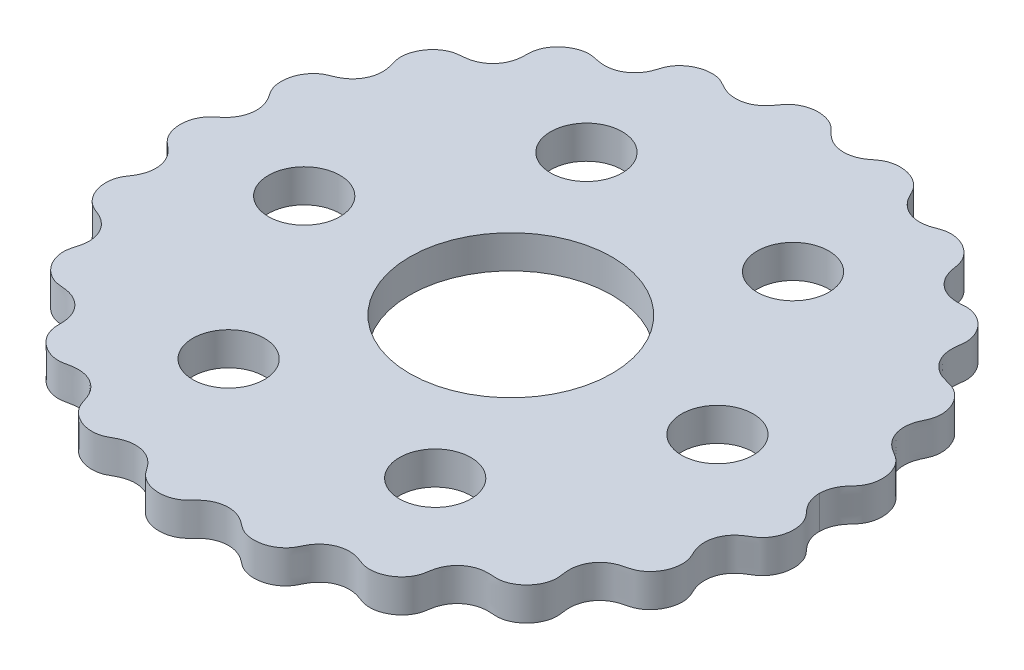
SolidWorks part; units mm, degrees
ref_plane "Front Plane" through (0, 0, 0) normal (0, 0, 1) x (1, 0, 0)
ref_plane "Top Plane" through (0, 0, 0) normal (0, 1, 0) x (1, 0, 0)
ref_plane "Right Plane" through (0, 0, 0) normal (1, 0, 0) x (0, 0, -1)
sketch "Sketch1" plane through (0, 0, 0) normal (0, 1, 0) x (1, 0, 0)
  line L0 (-58.2641, -0.8721) -> (57.7359, -0.8721) construction
  line L1 (1.7359, -0.8721) -> (1.7359, 57.2699) construction
  line L2 (1.7359, -0.8721) -> (1.7359, -59.0142) construction
  line L3 (-0.2641, -69.7644) -> (-0.2641, 70.5566) construction
  circle A0 centre (-0.2641, -0.8721) radius 63 construction
  circle A23 centre (1.7359, -0.8721) radius 37.5 construction
  circle A24 centre (-35.7641, -0.8721) radius 6.5
  circle A25 centre (-17.0141, 31.6038) radius 6.5
  circle A26 centre (20.4859, 31.6038) radius 6.5
  circle A27 centre (39.2359, -0.8721) radius 6.5
  circle A28 centre (20.4859, -33.3481) radius 6.5
  circle A29 centre (-17.0141, -33.3481) radius 6.5
  circle A37 centre (1.7359, -0.8721) radius 18.35
  spline S0 degree 4 poles (57.7091, 12.498) (57.878, 12.389) (58.2202, 12.1788) (58.75, 11.8893) (59.3907, 11.3973) (60.0214, 10.7095) (60.5813, 9.8085) (61.0058, 8.6748) (61.1955, 7.3302) (61.0908, 6.0677) (60.7435, 4.9487) (60.2801, 4.1321) (59.83, 3.5913) (59.4315, 3.1644) (59.1244, 2.811) (58.7965, 2.3918) (58.5194, 1.9674) (58.2923, 1.5442) (58.1126, 1.1275) (57.9906, 0.7856) (57.8914, 0.4364) (57.8251, 0.1259) (57.7831, -0.1439) (57.7603, -0.3468) (57.7488, -0.4924) (57.7402, -0.6503) (57.7355, -0.8102) (57.7353, -0.9181) (57.7394, -1.0706) (57.7465, -1.2185) (57.7568, -1.3606) (57.7782, -1.564) (57.8193, -1.8402) (57.8855, -2.1574) (57.9855, -2.5144) (58.1092, -2.8638) (58.2558, -3.2043) (58.4393, -3.5643) (58.665, -3.9391) (58.9372, -4.3234) (59.2571, -4.7132) (59.5962, -5.0858) (59.9358, -5.4582) (60.3214, -5.9576) (60.6604, -6.5603) (60.9245, -7.2626) (61.13, -8.2337) (61.1724, -9.3303) (60.9716, -10.5841) (60.4579, -11.8202) (59.7514, -12.811) (58.9127, -13.5486) (58.0252, -14.0251) (57.0958, -14.6302) (56.2107, -15.47) (55.4688, -16.595) (55.0111, -17.9962) (54.951, -19.3674) (55.1999, -20.6093) (55.6274, -21.6646) (56.103, -22.5667) (56.3981, -23.6738) (56.4238, -24.9379) (56.1285, -26.2986) (55.456, -27.6601) (54.5568, -28.7133) (53.5462, -29.4477) (52.5224, -29.8657) (51.5811, -30.0467) (50.5652, -30.3482) (49.5187, -30.8634) (48.5105, -31.6766) (47.6661, -32.8195) (47.2272, -33.9443) (47.0641, -34.9162) (47.0436, -35.6628) (47.0698, -36.1739) (47.1288, -36.6821) (47.2056, -37.1875) (47.2615, -37.6964) (47.2635, -38.2089) (47.2028, -38.7861) (47.0569, -39.4186) (46.8065, -40.0912) (46.4345, -40.7833) (45.8852, -41.5463) (45.1085, -42.3223) (44.1594, -42.9564) (43.1695, -43.3403) (42.3593, -43.4895) (41.7709, -43.5172) (41.3006, -43.4968) (40.8315, -43.4622) (40.3613, -43.4427) (39.825, -43.4512) (39.2256, -43.5117) (38.3919, -43.6889) (37.3515, -44.1083) (36.2639, -44.8727) (35.3819, -45.9667) (34.897, -47.0193) (34.6633, -47.8867) (34.5491, -48.5206) (34.4731, -49.0298) (34.371, -49.5352) (34.2144, -50.027) (33.9034, -50.729) (33.3353, -51.5818) (32.4167, -52.4771) (31.0868, -53.2449) (29.8522, -53.5928) (28.8295, -53.6584) (28.0661, -53.5767) (27.5619, -53.4665) (27.0731, -53.3022) (26.5941, -53.1133) (26.1093, -52.9391) (25.6142, -52.7956) (24.8615, -52.6402) (23.8372, -52.5777) (22.5776, -52.7745) (21.2036, -53.4123) (20.2572, -54.2235) (19.66, -54.9905) (19.2905, -55.6079) (19.0722, -56.0249) (18.8677, -56.4484) (18.6502, -56.8659) (18.3955, -57.2625) (18.1023, -57.6313) (17.6128, -58.1373) (16.8639, -58.7066) (15.9465, -59.159) (14.8862, -59.4436) (13.9507, -59.5378) (13.1654, -59.5139) (12.4577, -59.3944) (11.837, -59.2046) (11.3067, -58.9685) (10.8639, -58.7106) (10.4512, -58.4077) (10.0519, -58.0885) (9.6412, -57.7832) (9.2117, -57.505) (8.5549, -57.1495) (7.6317, -56.8048) (6.4381, -56.6225) (5.0261, -56.7823) (3.8178, -57.2488) (2.8483, -57.8975) (2.0793, -58.6266) (1.4519, -59.3513) (0.578, -60.0289) (-0.5633, -60.537) (-1.925, -60.7891) (-3.4404, -60.6907) (-4.7664, -60.2661) (-5.8482, -59.6118) (-6.6595, -58.8026) (-7.203, -57.9397) (-7.9031, -57.0419) (-8.8542, -56.2054) (-10.0718, -55.5718) (-11.5141, -55.2676) (-12.8593, -55.3476) (-14.0291, -55.6943) (-15.0179, -56.1965) (-15.8742, -56.7269) (-16.9324, -57.0844) (-18.1437, -57.2009) (-19.4713, -57.0276) (-20.831, -56.5084) (-21.9495, -55.7397) (-22.7899, -54.8119) (-23.3378, -53.8167) (-23.6076, -52.8425) (-23.9936, -51.783) (-24.6344, -50.7033) (-25.5969, -49.7156) (-26.8973, -48.9648) (-28.2339, -48.6251) (-29.4894, -48.61) (-30.6, -48.8054) (-31.5785, -49.0589) (-32.7144, -49.082) (-33.938, -48.8181) (-35.1631, -48.2338) (-36.2926, -47.3159) (-37.1064, -46.2527) (-37.6111, -45.1455) (-37.8307, -44.0504) (-37.7995, -43.0436) (-37.8589, -41.9361) (-38.1436, -40.7497) (-38.7469, -39.5447) (-39.7315, -38.4478) (-40.889, -37.7101) (-42.0889, -37.3047) (-43.2166, -37.1473) (-44.2356, -37.1081) (-45.342, -36.81) (-46.4495, -36.2003) (-47.4805, -35.2642) (-48.3229, -34.0011) (-48.786, -32.6958) (-48.9158, -31.4533) (-48.7836, -30.4772) (-48.5691, -29.7915) (-48.37, -29.1026) (-48.1967, -28.3012) (-48.1293, -27.2576) (-48.3283, -25.9778) (-48.8967, -24.6752) (-49.6508, -23.7326) (-50.4112, -23.1055) (-51.0474, -22.7144) (-51.5032, -22.4815) (-51.9728, -22.2785) (-52.449, -22.0923) (-52.9176, -21.8863) (-53.3624, -21.6318) (-53.832, -21.2906) (-54.3068, -20.8479) (-54.7641, -20.2948) (-55.1775, -19.6266) (-55.5635, -18.7694) (-55.8473, -17.7088) (-55.9219, -16.5698) (-55.7594, -15.5205) (-55.4834, -14.7443) (-55.2132, -14.2209) (-54.9604, -13.8237) (-54.6959, -13.4349) (-54.4439, -13.0374) (-54.1832, -12.5687) (-53.9359, -12.0193) (-53.6724, -11.2087) (-53.5424, -10.2882) (-53.5821, -9.3512) (-53.794, -8.4338) (-54.0692, -7.7195) (-54.4733, -6.9919) (-54.9442, -6.3815) (-55.4436, -5.8807) (-55.9354, -5.465) (-56.3384, -5.1445) (-56.7251, -4.8034) (-57.0727, -4.4218) (-57.3568, -4.0324) (-57.5855, -3.6469) (-57.7674, -3.2749) (-57.9102, -2.9223) (-58.029, -2.5612) (-58.1239, -2.1926) (-58.1861, -1.8664) (-58.2246, -1.5821) (-58.2446, -1.3733) (-58.2542, -1.228) (-58.2609, -1.076) (-58.2645, -0.9274) (-58.2646, -0.8251) (-58.2612, -0.682) (-58.2553, -0.539) (-58.2469, -0.4008) (-58.2292, -0.2042) (-58.1952, 0.0622) (-58.1403, 0.3703) (-58.0565, 0.7175) (-57.9516, 1.0593) (-57.8255, 1.3936) (-57.6656, 1.747) (-57.4652, 2.1143) (-57.2171, 2.4887) (-56.9137, 2.8602) (-56.5739, 3.1987) (-56.2061, 3.5056) (-55.8327, 3.8052) (-55.4709, 4.1192) (-55.0869, 4.4965) (-54.6983, 4.9508) (-54.2262, 5.6417) (-53.7783, 6.6204) (-53.5163, 7.8522) (-53.5816, 9.0569) (-53.8273, 9.992) (-54.1104, 10.6706) (-54.343, 11.1216) (-54.6063, 11.5553) (-54.8896, 11.9756) (-55.1688, 12.399) (-55.4088, 12.8467) (-55.5509, 13.2002) (-55.629, 13.4414) (-55.6639, 13.5633) knots 0 0 0 0 0 0.003358 0.006716 0.010075 0.013433 0.018886 0.024339 0.030148 0.035957 0.039866 0.043775 0.045729 0.047683 0.049638 0.051592 0.054624 0.05614 0.057656 0.059172 0.060688 0.062203 0.062961 0.063719 0.064151 0.064583 0.065447 0.066221 0.066608 0.066995 0.067769 0.068543 0.070091 0.071639 0.073187 0.074735 0.076283 0.077831 0.079936 0.082042 0.084147 0.086253 0.088359 0.090464 0.094675 0.097759 0.100843 0.10701 0.112905 0.118801 0.122998 0.127195 0.131392 0.135589 0.141508 0.147428 0.153675 0.159922 0.164171 0.16842 0.172669 0.176918 0.18314 0.189363 0.195705 0.202048 0.206045 0.210043 0.21404 0.218037 0.223723 0.229409 0.235467 0.241525 0.243662 0.245799 0.247936 0.250073 0.25221 0.254347 0.256484 0.258621 0.261894 0.265168 0.268441 0.271715 0.277567 0.283419 0.287351 0.289317 0.291283 0.293249 0.295215 0.297181 0.299147 0.302208 0.305269 0.311391 0.317768 0.324145 0.328449 0.330601 0.332753 0.334905 0.337058 0.33921 0.341362 0.347715 0.354068 0.360421 0.366774 0.368926 0.371078 0.37323 0.375382 0.377534 0.379686 0.381838 0.383991 0.390367 0.396744 0.402867 0.408989 0.410955 0.412921 0.414887 0.416852 0.418818 0.420784 0.42275 0.424716 0.430568 0.43642 0.439694 0.442968 0.446241 0.449515 0.451652 0.453789 0.455926 0.458063 0.4602 0.462337 0.464473 0.46661 0.472669 0.478727 0.484412 0.490098 0.494096 0.498093 0.50209 0.506088 0.51243 0.518773 0.524995 0.531217 0.535466 0.539716 0.543965 0.548214 0.554461 0.560708 0.566627 0.572547 0.576744 0.580941 0.585138 0.589335 0.59523 0.601125 0.607293 0.61346 0.617671 0.621882 0.626094 0.630305 0.636497 0.642688 0.64888 0.655072 0.659283 0.663494 0.667705 0.671916 0.678084 0.684251 0.690147 0.696042 0.700239 0.704436 0.708633 0.71283 0.718749 0.724669 0.730916 0.737163 0.741412 0.745661 0.74991 0.754159 0.760382 0.766604 0.772946 0.779289 0.783286 0.787284 0.789282 0.791281 0.795279 0.800964 0.80665 0.812708 0.818766 0.820903 0.82304 0.825177 0.827314 0.829451 0.831588 0.833725 0.835862 0.839135 0.842409 0.845683 0.848956 0.854808 0.860661 0.864592 0.866558 0.868524 0.87049 0.872456 0.874422 0.876388 0.879449 0.88251 0.888632 0.891821 0.895009 0.898198 0.901386 0.90569 0.907842 0.909994 0.912147 0.914299 0.916451 0.918603 0.920191 0.921779 0.923368 0.924956 0.926544 0.928132 0.928926 0.929721 0.930118 0.930515 0.931309 0.932055 0.932428 0.932802 0.933548 0.934294 0.935787 0.937279 0.938772 0.940265 0.941757 0.94325 0.945251 0.947252 0.949253 0.951254 0.953255 0.955255 0.957256 0.959257 0.962245 0.965233 0.971209 0.97713 0.983052 0.98517 0.987289 0.989407 0.991526 0.993644 0.995763 0.997881 1 1 1 1 1 construction
  spline S1 degree 4 poles (57.7359, -0.8721) (57.7359, -0.9122) (57.7367, -0.9728) (57.7394, -1.0706) (57.7465, -1.2185) (57.7568, -1.3606) (57.7782, -1.564) (57.8193, -1.8402) (57.8855, -2.1574) (57.9855, -2.5144) (58.1092, -2.8638) (58.2558, -3.2043) (58.4393, -3.5643) (58.665, -3.9391) (58.9372, -4.3234) (59.2571, -4.7132) (59.5962, -5.0858) (59.9358, -5.4582) (60.3214, -5.9576) (60.6604, -6.5603) (60.9245, -7.2626) (61.13, -8.2337) (61.1724, -9.3303) (60.9716, -10.5841) (60.4579, -11.8202) (59.7514, -12.811) (58.9127, -13.5486) (58.0252, -14.0251) (57.0958, -14.6302) (56.2107, -15.47) (55.4688, -16.595) (55.0111, -17.9962) (54.951, -19.3674) (55.1999, -20.6093) (55.6274, -21.6646) (56.103, -22.5667) (56.3981, -23.6738) (56.4238, -24.9379) (56.1285, -26.2986) (55.456, -27.6601) (54.5568, -28.7133) (53.5462, -29.4477) (52.5224, -29.8657) (51.5811, -30.0467) (50.5652, -30.3482) (49.5187, -30.8634) (48.5105, -31.6766) (47.6661, -32.8195) (47.2272, -33.9443) (47.0641, -34.9162) (47.0436, -35.6628) (47.0698, -36.1739) (47.1288, -36.6821) (47.2056, -37.1875) (47.2615, -37.6964) (47.2635, -38.2089) (47.2028, -38.7861) (47.0569, -39.4186) (46.8065, -40.0912) (46.4345, -40.7833) (45.8852, -41.5463) (45.1085, -42.3223) (44.1594, -42.9564) (43.1695, -43.3403) (42.3593, -43.4895) (41.7709, -43.5172) (41.3006, -43.4968) (40.8315, -43.4622) (40.3613, -43.4427) (39.825, -43.4512) (39.2256, -43.5117) (38.3919, -43.6889) (37.3515, -44.1083) (36.2639, -44.8727) (35.3819, -45.9667) (34.897, -47.0193) (34.6633, -47.8867) (34.5491, -48.5206) (34.4731, -49.0298) (34.371, -49.5352) (34.2144, -50.027) (33.9034, -50.729) (33.3353, -51.5818) (32.4167, -52.4771) (31.0868, -53.2449) (29.8522, -53.5928) (28.8295, -53.6584) (28.0661, -53.5767) (27.5619, -53.4665) (27.0731, -53.3022) (26.5941, -53.1133) (26.1093, -52.9391) (25.6142, -52.7956) (24.8615, -52.6402) (23.8372, -52.5777) (22.5776, -52.7745) (21.2036, -53.4123) (20.2572, -54.2235) (19.66, -54.9905) (19.2905, -55.6079) (19.0722, -56.0249) (18.8677, -56.4484) (18.6502, -56.8659) (18.3955, -57.2625) (18.1023, -57.6313) (17.6128, -58.1373) (16.8639, -58.7066) (15.9465, -59.159) (14.8862, -59.4436) (13.9507, -59.5378) (13.1654, -59.5139) (12.4577, -59.3944) (11.837, -59.2046) (11.3067, -58.9685) (10.8639, -58.7106) (10.4512, -58.4077) (10.0519, -58.0885) (9.6412, -57.7832) (9.2117, -57.505) (8.5549, -57.1495) (7.6317, -56.8048) (6.4381, -56.6225) (5.0261, -56.7823) (3.8178, -57.2488) (2.8483, -57.8975) (2.0793, -58.6266) (1.4519, -59.3513) (0.578, -60.0289) (-0.5633, -60.537) (-1.925, -60.7891) (-3.4404, -60.6907) (-4.7664, -60.2661) (-5.8482, -59.6118) (-6.6595, -58.8026) (-7.203, -57.9397) (-7.9031, -57.0419) (-8.8542, -56.2054) (-10.0718, -55.5718) (-11.5141, -55.2676) (-12.8593, -55.3476) (-14.0291, -55.6943) (-15.0179, -56.1965) (-15.8742, -56.7269) (-16.9324, -57.0844) (-18.1437, -57.2009) (-19.4713, -57.0276) (-20.831, -56.5084) (-21.9495, -55.7397) (-22.7899, -54.8119) (-23.3378, -53.8167) (-23.6076, -52.8425) (-23.9936, -51.783) (-24.6344, -50.7033) (-25.5969, -49.7156) (-26.8973, -48.9648) (-28.2339, -48.6251) (-29.4894, -48.61) (-30.6, -48.8054) (-31.5785, -49.0589) (-32.7144, -49.082) (-33.938, -48.8181) (-35.1631, -48.2338) (-36.2926, -47.3159) (-37.1064, -46.2527) (-37.6111, -45.1455) (-37.8307, -44.0504) (-37.7995, -43.0436) (-37.8589, -41.9361) (-38.1436, -40.7497) (-38.7469, -39.5447) (-39.7315, -38.4478) (-40.889, -37.7101) (-42.0889, -37.3047) (-43.2166, -37.1473) (-44.2356, -37.1081) (-45.342, -36.81) (-46.4495, -36.2003) (-47.4805, -35.2642) (-48.3229, -34.0011) (-48.786, -32.6958) (-48.9158, -31.4533) (-48.7836, -30.4772) (-48.5691, -29.7915) (-48.37, -29.1026) (-48.1967, -28.3012) (-48.1293, -27.2576) (-48.3283, -25.9778) (-48.8967, -24.6752) (-49.6508, -23.7326) (-50.4112, -23.1055) (-51.0474, -22.7144) (-51.5032, -22.4815) (-51.9728, -22.2785) (-52.449, -22.0923) (-52.9176, -21.8863) (-53.3624, -21.6318) (-53.832, -21.2906) (-54.3068, -20.8479) (-54.7641, -20.2948) (-55.1775, -19.6266) (-55.5635, -18.7694) (-55.8473, -17.7088) (-55.9219, -16.5698) (-55.7594, -15.5205) (-55.4834, -14.7443) (-55.2132, -14.2209) (-54.9604, -13.8237) (-54.6959, -13.4349) (-54.4439, -13.0374) (-54.1832, -12.5687) (-53.9359, -12.0193) (-53.6724, -11.2087) (-53.5424, -10.2882) (-53.5821, -9.3512) (-53.794, -8.4338) (-54.0692, -7.7195) (-54.4733, -6.9919) (-54.9442, -6.3815) (-55.4436, -5.8807) (-55.9354, -5.465) (-56.3384, -5.1445) (-56.7251, -4.8034) (-57.0727, -4.4218) (-57.3568, -4.0324) (-57.5855, -3.6469) (-57.7674, -3.2749) (-57.9102, -2.9223) (-58.029, -2.5612) (-58.1239, -2.1926) (-58.1861, -1.8664) (-58.2246, -1.5821) (-58.2446, -1.3733) (-58.2542, -1.228) (-58.2609, -1.076) (-58.2633, -0.9749) (-58.2641, -0.9133) (-58.2641, -0.8721) knots 0.065447 0.065447 0.065447 0.065447 0.065447 0.066221 0.066608 0.066995 0.067769 0.068543 0.070091 0.071639 0.073187 0.074735 0.076283 0.077831 0.079936 0.082042 0.084147 0.086253 0.088359 0.090464 0.094675 0.097759 0.100843 0.10701 0.112905 0.118801 0.122998 0.127195 0.131392 0.135589 0.141508 0.147428 0.153675 0.159922 0.164171 0.16842 0.172669 0.176918 0.18314 0.189363 0.195705 0.202048 0.206045 0.210043 0.21404 0.218037 0.223723 0.229409 0.235467 0.241525 0.243662 0.245799 0.247936 0.250073 0.25221 0.254347 0.256484 0.258621 0.261894 0.265168 0.268441 0.271715 0.277567 0.283419 0.287351 0.289317 0.291283 0.293249 0.295215 0.297181 0.299147 0.302208 0.305269 0.311391 0.317768 0.324145 0.328449 0.330601 0.332753 0.334905 0.337058 0.33921 0.341362 0.347715 0.354068 0.360421 0.366774 0.368926 0.371078 0.37323 0.375382 0.377534 0.379686 0.381838 0.383991 0.390367 0.396744 0.402867 0.408989 0.410955 0.412921 0.414887 0.416852 0.418818 0.420784 0.42275 0.424716 0.430568 0.43642 0.439694 0.442968 0.446241 0.449515 0.451652 0.453789 0.455926 0.458063 0.4602 0.462337 0.464473 0.46661 0.472669 0.478727 0.484412 0.490098 0.494096 0.498093 0.50209 0.506088 0.51243 0.518773 0.524995 0.531217 0.535466 0.539716 0.543965 0.548214 0.554461 0.560708 0.566627 0.572547 0.576744 0.580941 0.585138 0.589335 0.59523 0.601125 0.607293 0.61346 0.617671 0.621882 0.626094 0.630305 0.636497 0.642688 0.64888 0.655072 0.659283 0.663494 0.667705 0.671916 0.678084 0.684251 0.690147 0.696042 0.700239 0.704436 0.708633 0.71283 0.718749 0.724669 0.730916 0.737163 0.741412 0.745661 0.74991 0.754159 0.760382 0.766604 0.772946 0.779289 0.783286 0.787284 0.789282 0.791281 0.795279 0.800964 0.80665 0.812708 0.818766 0.820903 0.82304 0.825177 0.827314 0.829451 0.831588 0.833725 0.835862 0.839135 0.842409 0.845683 0.848956 0.854808 0.860661 0.864592 0.866558 0.868524 0.87049 0.872456 0.874422 0.876388 0.879449 0.88251 0.888632 0.891821 0.895009 0.898198 0.901386 0.90569 0.907842 0.909994 0.912147 0.914299 0.916451 0.918603 0.920191 0.921779 0.923368 0.924956 0.926544 0.928132 0.928926 0.929721 0.930118 0.930515 0.931309 0.931309 0.931309 0.931309 0.931309
  spline S2 degree 4 poles (57.7359, -0.8721) (57.7359, -0.832) (57.7367, -0.7715) (57.7394, -0.6736) (57.7465, -0.5257) (57.7568, -0.3837) (57.7782, -0.1803) (57.8193, 0.0959) (57.8855, 0.4131) (57.9855, 0.7702) (58.1092, 1.1196) (58.2558, 1.4601) (58.4393, 1.82) (58.665, 2.1948) (58.9372, 2.5792) (59.2571, 2.9689) (59.5962, 3.3416) (59.9358, 3.7139) (60.3214, 4.2134) (60.6604, 4.8161) (60.9245, 5.5184) (61.13, 6.4894) (61.1724, 7.586) (60.9716, 8.8398) (60.4579, 10.0759) (59.7514, 11.0668) (58.9127, 11.8044) (58.0252, 12.2808) (57.0958, 12.886) (56.2107, 13.7258) (55.4688, 14.8507) (55.0111, 16.2519) (54.951, 17.6231) (55.1999, 18.865) (55.6274, 19.9203) (56.103, 20.8224) (56.3981, 21.9296) (56.4238, 23.1937) (56.1285, 24.5544) (55.456, 25.9158) (54.5568, 26.9691) (53.5462, 27.7034) (52.5224, 28.1215) (51.5811, 28.3025) (50.5652, 28.6039) (49.5187, 29.1192) (48.5105, 29.9323) (47.6661, 31.0752) (47.2272, 32.2) (47.0641, 33.1719) (47.0436, 33.9185) (47.0698, 34.4296) (47.1288, 34.9379) (47.2056, 35.4433) (47.2615, 35.9521) (47.2635, 36.4646) (47.2028, 37.0419) (47.0569, 37.6744) (46.8065, 38.347) (46.4345, 39.0391) (45.8852, 39.8021) (45.1085, 40.578) (44.1594, 41.2122) (43.1695, 41.5961) (42.3593, 41.7452) (41.7709, 41.7729) (41.3006, 41.7526) (40.8315, 41.7179) (40.3613, 41.6984) (39.825, 41.707) (39.2256, 41.7675) (38.3919, 41.9446) (37.3515, 42.3641) (36.2639, 43.1285) (35.3819, 44.2224) (34.897, 45.2751) (34.6633, 46.1425) (34.5491, 46.7763) (34.4731, 47.2855) (34.371, 47.791) (34.2144, 48.2827) (33.9034, 48.9848) (33.3353, 49.8376) (32.4167, 50.7328) (31.0868, 51.5006) (29.8522, 51.8486) (28.8295, 51.9142) (28.0661, 51.8325) (27.5619, 51.7222) (27.0731, 51.558) (26.5941, 51.369) (26.1093, 51.1948) (25.6142, 51.0513) (24.8615, 50.896) (23.8372, 50.8335) (22.5776, 51.0303) (21.2036, 51.6681) (20.2572, 52.4793) (19.66, 53.2463) (19.2905, 53.8637) (19.0722, 54.2807) (18.8677, 54.7042) (18.6502, 55.1217) (18.3955, 55.5182) (18.1023, 55.8871) (17.6128, 56.3931) (16.8639, 56.9623) (15.9465, 57.4147) (14.8862, 57.6993) (13.9507, 57.7936) (13.1654, 57.7697) (12.4577, 57.6502) (11.837, 57.4604) (11.3067, 57.2243) (10.8639, 56.9663) (10.4512, 56.6635) (10.0519, 56.3442) (9.6412, 56.039) (9.2117, 55.7608) (8.5549, 55.4052) (7.6317, 55.0605) (6.4381, 54.8783) (5.0261, 55.038) (3.8178, 55.5046) (2.8483, 56.1532) (2.0793, 56.8824) (1.4519, 57.607) (0.578, 58.2846) (-0.5633, 58.7927) (-1.925, 59.0448) (-3.4404, 58.9465) (-4.7664, 58.5219) (-5.8482, 57.8675) (-6.6595, 57.0584) (-7.203, 56.1955) (-7.9031, 55.2976) (-8.8542, 54.4611) (-10.0718, 53.8275) (-11.5141, 53.5233) (-12.8593, 53.6033) (-14.0291, 53.95) (-15.0179, 54.4523) (-15.8742, 54.9827) (-16.9324, 55.3402) (-18.1437, 55.4566) (-19.4713, 55.2834) (-20.831, 54.7642) (-21.9495, 53.9955) (-22.7899, 53.0677) (-23.3378, 52.0724) (-23.6076, 51.0983) (-23.9936, 50.0387) (-24.6344, 48.959) (-25.5969, 47.9713) (-26.8973, 47.2206) (-28.2339, 46.8809) (-29.4894, 46.8658) (-30.6, 47.0612) (-31.5785, 47.3147) (-32.7144, 47.3378) (-33.938, 47.0739) (-35.1631, 46.4896) (-36.2926, 45.5716) (-37.1064, 44.5085) (-37.6111, 43.4013) (-37.8307, 42.3061) (-37.7995, 41.2994) (-37.8589, 40.1919) (-38.1436, 39.0054) (-38.7469, 37.8004) (-39.7315, 36.7035) (-40.889, 35.9659) (-42.0889, 35.5604) (-43.2166, 35.4031) (-44.2356, 35.3638) (-45.342, 35.0658) (-46.4495, 34.4561) (-47.4805, 33.52) (-48.3229, 32.2568) (-48.786, 30.9516) (-48.9158, 29.709) (-48.7836, 28.733) (-48.5691, 28.0472) (-48.37, 27.3583) (-48.1967, 26.557) (-48.1293, 25.5134) (-48.3283, 24.2335) (-48.8967, 22.9309) (-49.6508, 21.9883) (-50.4112, 21.3612) (-51.0474, 20.9701) (-51.5032, 20.7373) (-51.9728, 20.5342) (-52.449, 20.3481) (-52.9176, 20.1421) (-53.3624, 19.8875) (-53.832, 19.5464) (-54.3068, 19.1037) (-54.7641, 18.5505) (-55.1775, 17.8824) (-55.5635, 17.0251) (-55.8473, 15.9646) (-55.9219, 14.8255) (-55.7594, 13.7763) (-55.4834, 13) (-55.2132, 12.4766) (-54.9604, 12.0795) (-54.6959, 11.6906) (-54.4439, 11.2931) (-54.1832, 10.8244) (-53.9359, 10.2751) (-53.6724, 9.4644) (-53.5424, 8.544) (-53.5821, 7.607) (-53.794, 6.6896) (-54.0692, 5.9752) (-54.4733, 5.2476) (-54.9442, 4.6372) (-55.4436, 4.1365) (-55.9354, 3.7207) (-56.3384, 3.4003) (-56.7251, 3.0592) (-57.0727, 2.6775) (-57.3568, 2.2881) (-57.5855, 1.9027) (-57.7674, 1.5307) (-57.9102, 1.1781) (-58.029, 0.8169) (-58.1239, 0.4484) (-58.1861, 0.1221) (-58.2246, -0.1622) (-58.2446, -0.3709) (-58.2542, -0.5163) (-58.2609, -0.6682) (-58.2633, -0.7694) (-58.2641, -0.831) (-58.2641, -0.8721) knots 0.065447 0.065447 0.065447 0.065447 0.065447 0.066221 0.066608 0.066995 0.067769 0.068543 0.070091 0.071639 0.073187 0.074735 0.076283 0.077831 0.079936 0.082042 0.084147 0.086253 0.088359 0.090464 0.094675 0.097759 0.100843 0.10701 0.112905 0.118801 0.122998 0.127195 0.131392 0.135589 0.141508 0.147428 0.153675 0.159922 0.164171 0.16842 0.172669 0.176918 0.18314 0.189363 0.195705 0.202048 0.206045 0.210043 0.21404 0.218037 0.223723 0.229409 0.235467 0.241525 0.243662 0.245799 0.247936 0.250073 0.25221 0.254347 0.256484 0.258621 0.261894 0.265168 0.268441 0.271715 0.277567 0.283419 0.287351 0.289317 0.291283 0.293249 0.295215 0.297181 0.299147 0.302208 0.305269 0.311391 0.317768 0.324145 0.328449 0.330601 0.332753 0.334905 0.337058 0.33921 0.341362 0.347715 0.354068 0.360421 0.366774 0.368926 0.371078 0.37323 0.375382 0.377534 0.379686 0.381838 0.383991 0.390367 0.396744 0.402867 0.408989 0.410955 0.412921 0.414887 0.416852 0.418818 0.420784 0.42275 0.424716 0.430568 0.43642 0.439694 0.442968 0.446241 0.449515 0.451652 0.453789 0.455926 0.458063 0.4602 0.462337 0.464473 0.46661 0.472669 0.478727 0.484412 0.490098 0.494096 0.498093 0.50209 0.506088 0.51243 0.518773 0.524995 0.531217 0.535466 0.539716 0.543965 0.548214 0.554461 0.560708 0.566627 0.572547 0.576744 0.580941 0.585138 0.589335 0.59523 0.601125 0.607293 0.61346 0.617671 0.621882 0.626094 0.630305 0.636497 0.642688 0.64888 0.655072 0.659283 0.663494 0.667705 0.671916 0.678084 0.684251 0.690147 0.696042 0.700239 0.704436 0.708633 0.71283 0.718749 0.724669 0.730916 0.737163 0.741412 0.745661 0.74991 0.754159 0.760382 0.766604 0.772946 0.779289 0.783286 0.787284 0.789282 0.791281 0.795279 0.800964 0.80665 0.812708 0.818766 0.820903 0.82304 0.825177 0.827314 0.829451 0.831588 0.833725 0.835862 0.839135 0.842409 0.845683 0.848956 0.854808 0.860661 0.864592 0.866558 0.868524 0.87049 0.872456 0.874422 0.876388 0.879449 0.88251 0.888632 0.891821 0.895009 0.898198 0.901386 0.90569 0.907842 0.909994 0.912147 0.914299 0.916451 0.918603 0.920191 0.921779 0.923368 0.924956 0.926544 0.928132 0.928926 0.929721 0.930118 0.930515 0.931309 0.931309 0.931309 0.931309 0.931309
  dimension "D2" = 126
  dimension "D4" = 75
  dimension "D5" = 13
  dimension "D8" = 36.7
  dimension "D1" = 2
extrude "Boss-Extrude1" add sketch "Sketch1" along normal blind 6 contours S2 S1
extrude "Cut-Extrude1" cut sketch "Sketch1<3>" along normal blind 10 contours A24 | A25 | A26 | A27 | A28 | A37 | A29
sketch "Sketch1<3>" plane through (0, 0, 0) normal (0, 1, 0) x (1, 0, 0) same geometry as "Sketch1"
equation "\"R\"= 63mm"
equation "\"E\"= 2mm"
equation "\"Rr\"= 5"
equation "\"N\"= 22"
equation "\"M5\"= 5"
equation "\"SMALL_BEARING_DEPTH\"= 6MM"
equation "\"D1@Boss-Extrude1\"=\"SMALL_BEARING_DEPTH\""
